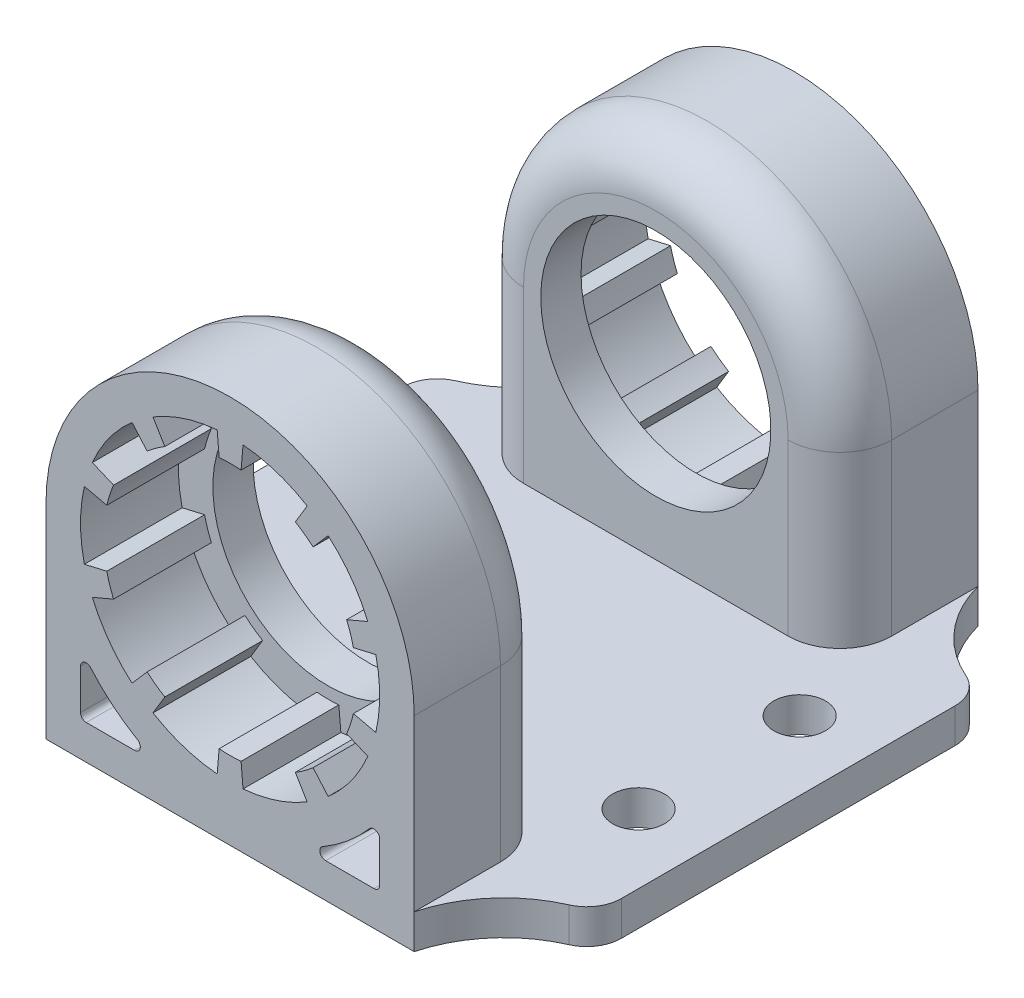
SolidWorks part; units mm, degrees
ref_plane "Alzado" through (0, 0, 0) normal (0, 0, 1) x (1, 0, 0)
ref_plane "Planta" through (0, 0, 0) normal (0, 1, 0) x (1, 0, 0)
ref_plane "Vista lateral" through (0, 0, 0) normal (1, 0, 0) x (0, 0, -1)
sketch "Croquis2" plane through (0, 0, 0) normal (0, 0, 1) x (1, 0, 0)
  line L1 (0, 0) -> (-32, 0)
  line L2 (0, 0) -> (0, 17.76)
  line L4 (-32, 0) -> (-32, 17.76)
  arc A0 (0, 17.76) -> (-32, 17.76) centre (-16, 17.76) ccw
  dimension "D1" = 32
  dimension "D2" = 17.76
extrude "Saliente-Extruir1" add sketch "Croquis2" along normal mid plane 12
sketch "Croquis3" plane through (0, 0, 6) normal (0, 0, 1) x (1, 0, 0)
  circle A0 centre (-16, 17.76) radius 4
  dimension "D1" = 8
extrude "Cortar-Extruir1" cut sketch "Croquis3" against normal through all
ref_plane "Plano1" through (-16, 0, 0) normal (-1, 0, 0) x (0, 0, 1)
sketch "Croquis4" plane through (0, 0, 6) normal (0, 0, 1) x (1, 0, 0)
  circle A0 centre (-16, 17.76) radius 13
  dimension "D1" = 26
extrude "Cortar-Extruir2" cut sketch "Croquis4" against normal blind 8.5
sketch "Croquis5" plane through (0, 0, -2.5) normal (0, 0, 1) x (1, 0, 0)
  circle A0 centre (-16, 17.76) radius 10
  dimension "D1" = 20
extrude "Cortar-Extruir3" cut sketch "Croquis5" against normal blind 8.5
sketch "Croquis6" plane through (0, 0, -6) normal (0, 0, -1) x (-1, 0, 0)
  line L0 (32, 17.76) -> (32, 0) construction
  line L1 (0, 0) -> (32, 0)
  line L2 (0, 0) -> (0, 3)
  line L3 (0, 3) -> (32, 3)
  line L4 (32, 0) -> (32, 3)
  dimension "D1" = 3
extrude "Saliente-Extruir2" add sketch "Croquis6" along normal blind 25
ref_plane "Plano2" through (0, 0, -18.5) normal (0, 0, -1) x (-1, 0, 0)
mirror "Simetría1" about plane through (0, 0, -18.5) normal (0, 0, -1) of "Cortar-Extruir3", "Cortar-Extruir2", "Saliente-Extruir1"
sketch "Croquis7" plane through (0, 0, 0) normal (0, 1, 0) x (1, 0, 0)
  line L0 (0, 43) -> (0, 31) construction
  line L1 (0, 36) -> (5, 36)
  line L2 (0, 36) -> (0, 1)
  line L3 (0, 1) -> (5, 1)
  line L4 (8, 33) -> (8, 4)
  line L5 (0, 43) -> (-32, 43) construction
  line L6 (-32, -6) -> (0, -6) construction
  line L7 (-16, 43) -> (-16, 38.616) construction
  line L8 (-32, 1) -> (-37, 1)
  line L9 (-40, 33) -> (-40, 4)
  line L10 (-32, 36) -> (-37, 36)
  line L11 (-32, 36) -> (-32, 1)
  arc A0 (5, 1) -> (8, 4) centre (5, 4) ccw
  arc A1 (5, 36) -> (8, 33) centre (5, 33) cw
  arc A2 (-37, 1) -> (-40, 4) centre (-37, 4) cw
  arc A3 (-37, 36) -> (-40, 33) centre (-37, 33) ccw
  dimension "D4" = 3
  dimension "D1" = 7
  dimension "D2" = 7
  dimension "D3" = 8
extrude "Saliente-Extruir3" add sketch "Croquis7" along normal blind 3
fillet "Redondeo1" radius 11 4 edges at (0, 1.5, -36) (0, 1.5, -1) (-32, 1.5, -1) (-32, 1.5, -36)
sketch "Croquis8" plane through (0, 3, 0) normal (0, 1, 0) x (1, 0, 0)
  line L0 (8, 4) -> (8, 33) construction
  line L2 (16.918, 18.5) -> (-16.918, 18.5) construction
  circle A0 centre (2, 25.5) radius 2.25
  circle A1 centre (2, 11.5) radius 2.25
  dimension "D1" = 4.5
  dimension "D2" = 6
  dimension "D3" = 7
extrude "Cortar-Extruir4" cut sketch "Croquis8" against normal through all
mirror "Simetría2" about plane through (-16, 0, 0) normal (-1, 0, 0) of "Cortar-Extruir4"
sketch "Croquis11" plane through (0, 0, 6) normal (0, 0, 1) x (1, 0, 0)
  line L0 (-17.125, 30.7112) -> (-16.9519, 28.7187)
  line L1 (-14.875, 30.7112) -> (-15.0481, 28.7187)
  line L2 (-16, 30.76) -> (-16, 28.76) construction
  circle A0 centre (-16, 17.76) radius 16 construction
  arc A2 (-15.0481, 28.7187) -> (-16.9519, 28.7187) centre (-16, 17.76) ccw
  circle A3 centre (-16, 17.76) radius 13 construction
  arc A4 (-14.875, 30.7112) -> (-17.125, 30.7112) centre (-16, 17.76) ccw
  dimension "D1" = 32
  dimension "D2" = 2.25
  dimension "D3" = 22
extrude "Saliente-Extruir4" add sketch "Croquis11" against normal up to surface (8.5 mm away) up to face at (-6, 17.76, -2.5)
pattern_circular "MatrizC1" count 10 every 36 about axis through (-16, 17.76, 6) along (0, 0, 1) of "Saliente-Extruir4"
mirror "Simetría3" about plane through (0, 0, -18.5) normal (0, 0, -1) of "MatrizC1", "Saliente-Extruir4"
fillet "Redondeo2" radius 4.5 6 edges at (0, 10.38, -6) (-32, 10.38, -6) (-16, 33.76, -6) (0, 10.38, -31) (-32, 10.38, -31) (-16, 33.76, -31)
sketch "Croquis12" plane through (0, 0, 6) normal (0, 0, 1) x (1, 0, 0)
  line L0 (-3, 3.5) -> (-3, 6.9897)
  line L1 (0, 3) -> (0, 17.76) construction
  line L2 (-3.5, 3) -> (-7.6993, 3)
  line L3 (-32, 0) -> (0, 0) construction
  arc A0 (-7.9508, 3.9321) -> (-3.8788, 7.316) centre (-16, 17.76) ccw
  arc A1 (-3, 3.5) -> (-3.5, 3) centre (-3.5, 3.5) cw
  arc A2 (-3, 6.9897) -> (-3.8788, 7.316) centre (-3.5, 6.9897) ccw
  arc A3 (-7.6993, 3) -> (-7.9508, 3.9321) centre (-7.6993, 3.5) cw
  point P9 (0, 0)
  dimension "D3" = 32
  dimension "D4" = 0.5
  dimension "D1" = 3
  dimension "D2" = 3
extrude "Cortar-Extruir5" cut sketch "Croquis12" against normal blind 9
mirror "Simetría4" about plane through (-16, 0, 0) normal (-1, 0, 0) of "Cortar-Extruir5"
mirror "Simetría5" about plane through (0, 0, -18.5) normal (0, 0, -1) of "Simetría4", "Cortar-Extruir5"
